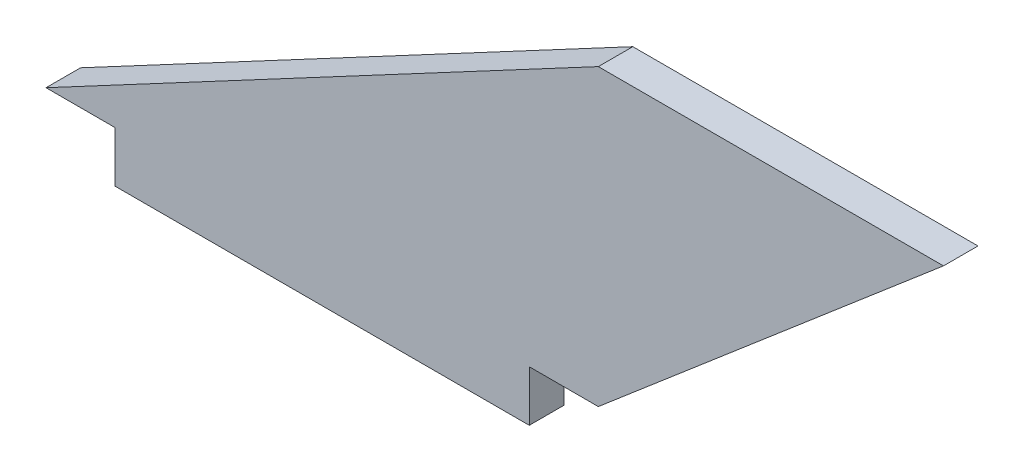
SolidWorks part; units mm, degrees
ref_plane "Front Plane" through (0, 0, 0) normal (0, 0, 1) x (1, 0, 0)
ref_plane "Top Plane" through (0, 0, 0) normal (0, 1, 0) x (1, 0, 0)
ref_plane "Right Plane" through (0, 0, 0) normal (1, 0, 0) x (0, 0, -1)
sketch "Sketch1" plane through (0, 0, 0) normal (0, 0, 1) x (1, 0, 0)
  line L0 (0, 0) -> (0, -7.351)
  line L1 (0, -7.351) -> (60, -7.351)
  line L2 (60, -7.351) -> (60, 0)
  line L3 (60, 0) -> (70, 0)
  line L4 (70, 0) -> (120, 42.649)
  line L5 (120, 42.649) -> (70, 42.649)
  line L6 (70, 42.649) -> (-10, 0)
  line L7 (-10, 0) -> (0, 0)
  dimension "D1" = 10
  dimension "D2" = 10
  dimension "D3" = 60
  dimension "D4" = 50
  dimension "D5" = 80
  dimension "D6" = 50
extrude "Boss-Extrude1" add sketch "Sketch1" along normal blind 5
